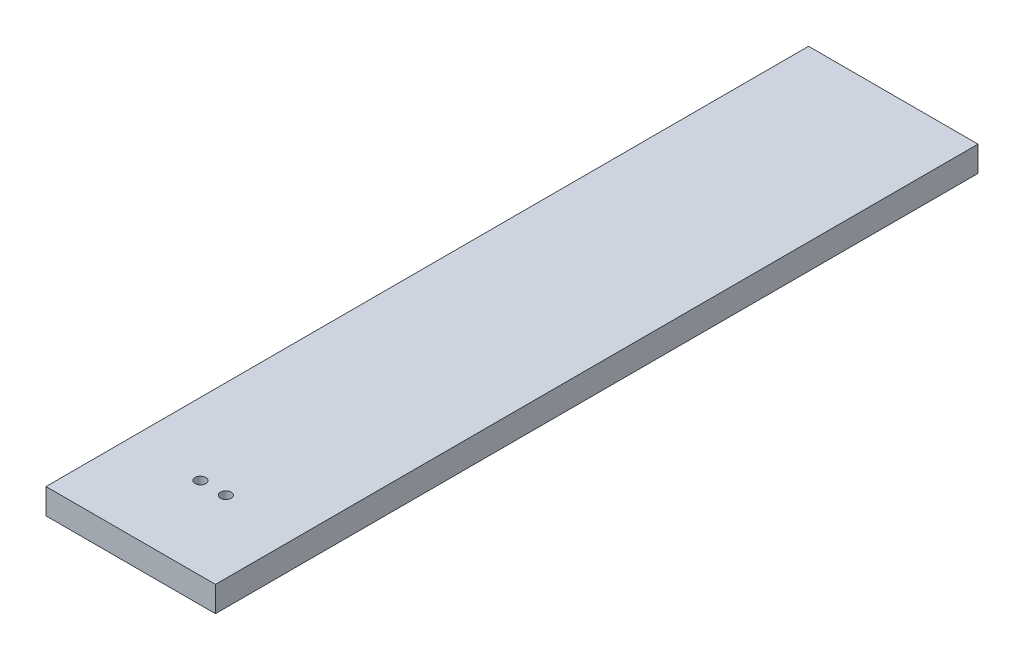
SolidWorks part; units mm, degrees
ref_plane "Front" through (0, 0, 0) normal (0, 0, 1) x (1, 0, 0)
ref_plane "Top" through (0, 0, 0) normal (0, 1, 0) x (1, 0, 0)
ref_plane "Right" through (0, 0, 0) normal (1, 0, 0) x (0, 0, -1)
sketch "Sketch1" plane through (0, 0, 0) normal (0, 1, 0) x (1, 0, 0)
  line L1 (-7.9375, 35.7188) -> (7.9375, 35.7188)
  line L2 (-7.9375, 35.7188) -> (-7.9375, -35.7188)
  line L3 (-7.9375, -35.7188) -> (7.9375, -35.7188)
  line L4 (7.9375, 35.7188) -> (7.9375, -35.7188)
  line L5 (-7.9375, 35.7188) -> (7.9375, -35.7188) construction
  line L6 (-7.9375, -35.7188) -> (7.9375, 35.7188) construction
  point P0 (0, 0)
  dimension "D1" = 15.875
  dimension "D2" = 71.4375
base flange "Base-Flange1" sketch "Sketch1" thickness 2.3812 reverse thickness direction no parameters "D1"=10
sketch "Sketch2" plane through (0, 0, 0) normal (0, 1, 0) x (1, 0, 0)
  line L0 (-1.19, -28) -> (1.19, -28) construction
  line L1 (0, -28) -> (0, 0) construction
  circle A0 centre (-1.19, -28) radius 0.5
  circle A1 centre (1.19, -28) radius 0.5
  dimension "D2" = 1
  dimension "D1" = 2.38
  dimension "D3" = 28
extrude "Cut-Extrude1" cut sketch "Sketch2" against normal through all normal cut yes
sketch "Bend-Lines1" [suppressed] plane through (0, 0, 0) normal (0, 1, 0) x (1, 0, 0)
sketch "Bounding-Box1" [suppressed] plane through (0, 0, 0) normal (0, 1, 0) x (1, 0, 0)
sheet metal parameters "Sheet-Metal1" thickness 2.3812 parameters "D1"=10
flat pattern "Flat-Pattern1" [suppressed]
sketch "Bend-Lines2" plane through (0, 0, 0) normal (0, 1, 0) x (1, 0, 0)
sketch "Bounding-Box2" [suppressed] plane through (0, 0, 0) normal (0, 1, 0) x (1, 0, 0)
sheet metal parameters "Sheet-Metal2" thickness 2.3812 parameters "D1"=10
flat pattern "Flat-Pattern1"
sketch "Bend-Lines2" plane through (0, 0, 0) normal (0, 1, 0) x (1, 0, 0)
sketch3d "Bounding-Box2" [suppressed]
  line L0 (-7.9375, 35.7188, 0) -> (-7.9375, -35.7188, 0) construction
  line L1 (7.9375, 35.7188, 0) -> (7.9375, -35.7188, 0) construction
  line L2 (-7.9375, 35.7188, 0) -> (7.9375, 35.7188, 0) construction
  line L3 (-7.9375, -35.7188, 0) -> (7.9375, -35.7188, 0) construction
